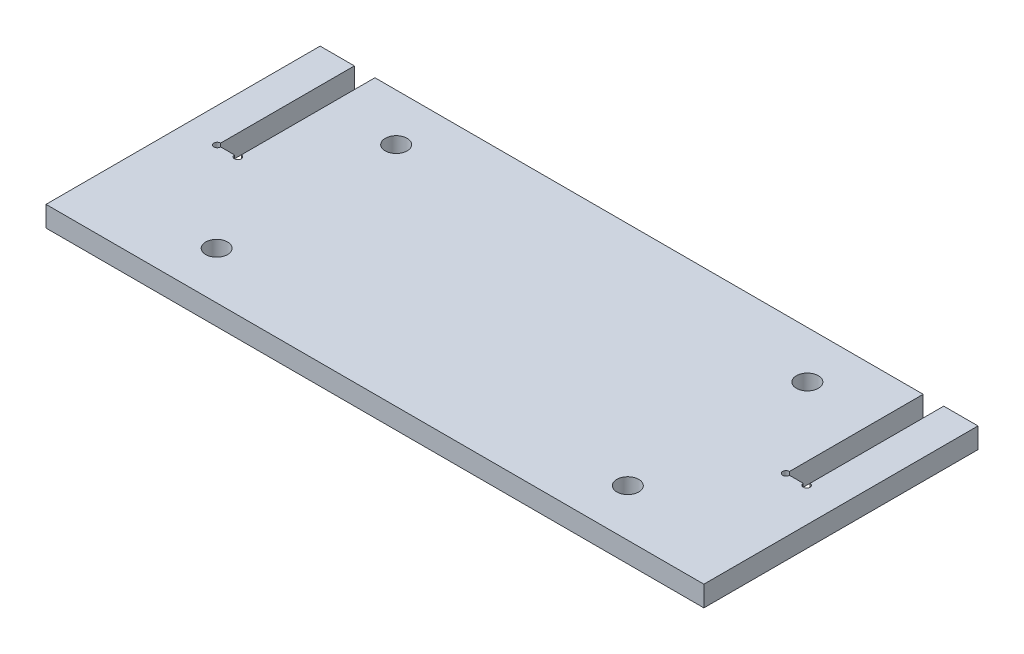
SolidWorks part; units mm, degrees
material "Acrylic (Medium-high impact)"
ref_plane "Front Plane" through (0, 0, 0) normal (0, 0, 1) x (1, 0, 0)
ref_plane "Top Plane" through (0, 0, 0) normal (0, 1, 0) x (1, 0, 0)
ref_plane "Right Plane" through (0, 0, 0) normal (1, 0, 0) x (0, 0, -1)
sketch "Sketch1" plane through (0, 0, 0) normal (0, 1, 0) x (1, 0, 0)
  line L0 (-30, 13.1) -> (30, -13.1) construction
  line L1 (-48, -20) -> (48, -20)
  line L2 (-48, -20) -> (-48, 20)
  line L3 (-48, 20) -> (-43, 20)
  line L4 (48, -20) -> (48, 20)
  line L5 (-48, -20) -> (48, 20) construction
  line L6 (-48, 20) -> (48, -20) construction
  line L7 (-30, 13.1) -> (-30, -13.1) construction
  line L8 (-30, -13.1) -> (30, -13.1) construction
  line L9 (30, -13.1) -> (30, 13.1) construction
  line L10 (-30, 13.1) -> (30, 13.1) construction
  line L11 (30, 13.1) -> (-30, -13.1) construction
  line L12 (-43, 20) -> (-43, 0)
  line L13 (-43, 0) -> (-40, 0)
  line L14 (-40, 0) -> (-40, 20)
  line L15 (40, 20) -> (40, 0)
  line L16 (40, 0) -> (43, 0)
  line L17 (43, 0) -> (43, 20)
  line L18 (-40, 20) -> (40, 20)
  line L19 (43, 20) -> (48, 20)
  circle A0 centre (-30, 13.1) radius 1.6
  circle A1 centre (30, 13.1) radius 1.6
  circle A2 centre (30, -13.1) radius 1.6
  circle A3 centre (-30, -13.1) radius 1.6
  point P0 (0, 0)
  dimension "D5" = 3.2
  dimension "D1" = 5
  dimension "D2" = 40
  dimension "D6" = 60
  dimension "D7" = 26.2
  dimension "D8" = 80
  dimension "D9" = 3
  dimension "D3" = 2
  dimension "D4" = 2
extrude "Boss-Extrude1" add sketch "Sketch1" along normal blind 3
sketch "Sketch2" plane through (0, 3, 0) normal (0, 1, 0) x (1, 0, 0)
  circle A0 centre (-43, 0) radius 0.5
  circle A1 centre (-40, 0) radius 0.5
  circle A2 centre (40, 0) radius 0.5
  circle A3 centre (43, 0) radius 0.5
  dimension "D1" = 1
extrude "Cut-Extrude1" cut sketch "Sketch2" against normal through all
